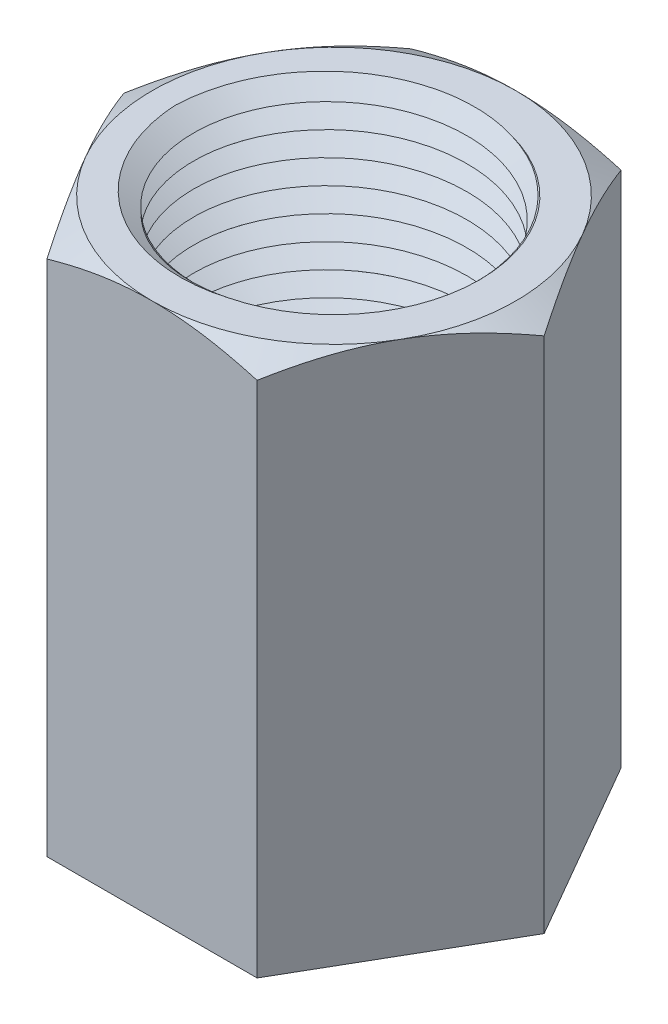
SolidWorks part; units mm, degrees
ref_plane "Front Plane" through (0, 0, 0) normal (0, 0, 1) x (1, 0, 0)
ref_plane "Top Plane" through (0, 0, 0) normal (0, 1, 0) x (1, 0, 0)
ref_plane "Right Plane" through (0, 0, 0) normal (1, 0, 0) x (0, 0, -1)
sketch "Sketch1" plane through (0, 0, 0) normal (0, 1, 0) x (1, 0, 0)
  line L1 (8.6603, 0) -> (4.3301, 7.5)
  line L2 (4.3301, 7.5) -> (-4.3301, 7.5)
  line L3 (-4.3301, 7.5) -> (-8.6603, 0)
  line L4 (-8.6603, 0) -> (-4.3301, -7.5)
  line L5 (-4.3301, -7.5) -> (4.3301, -7.5)
  line L6 (4.3301, -7.5) -> (8.6603, 0)
  circle A0 centre (0, 0) radius 7.5 construction
  dimension "D1" = 15
extrude "Boss-Extrude1" add sketch "Sketch1" along normal blind 22
sketch "Sketch2" plane through (0, 22, 0) normal (0, 1, 0) x (1, 0, 0)
  circle A0 centre (0, 0) radius 5.5
  dimension "D1" = 11
extrude "Cut-Extrude1" cut sketch "Sketch2" against normal blind 22
sketch "Sketch3" plane through (0, 22, 0) normal (0, 1, 0) x (1, 0, 0)
  circle A0 centre (0, 0) radius 7.5
extrude "Cut-Extrude2" cut sketch "Sketch3" against normal blind 1 draft 60 flip side to cut contours A0
chamfer "Chamfer2" distance 0.5 angle 45 1 edges at (0, 22, 5.5)
ref_plane "Plane1" through (0, 32, 0) normal (0, 1, 0) x (1, 0, 0)
sketch "Sketch4" plane through (0, 32, 0) normal (0, 1, 0) x (1, 0, 0)
  circle A0 centre (0, 0) radius 5.5 construction
  circle A1 centre (0, 0) radius 5.5
curve "Helix/Spiral1" pitch 1 height 34 radius 5.5 centre (0, 32, 0) axis (0, -1, 0) start towards (0, 0, 1)
sketch "Sketch6" plane through (0, 0, 0) normal (0, 0, 1) x (1, 0, 0)
  line L1 (-6.5, 32) -> (-5, 31.134)
  line L2 (-5, 31.134) -> (-5, 32.866)
  line L3 (-5, 32.866) -> (-6.5, 32)
  circle A0 centre (-5.5, 32) radius 0.5 construction
  spline S0 degree 3 poles (-5.5, 32) (-5.5, 31.9793) (-5.2126, 31.9373) (-3.9849, 31.8748) (-2.1484, 31.8122) (0.0163, 31.7495) (2.1786, 31.6869) (4.008, 31.6243) (5.225, 31.5617) (5.6436, 31.4991) (5.2, 31.4365) (3.9617, 31.3738) (2.1182, 31.3112) (-0.049, 31.2486) (-2.2087, 31.186) (-4.0309, 31.1234) (-5.2372, 31.0608) (-5.6433, 30.9982) (-5.1872, 30.9355) (-3.9384, 30.8729) (-2.0879, 30.8103) (0.0816, 30.7477) (2.2387, 30.6851) (4.0537, 30.6225) (5.2493, 30.5599) (5.6429, 30.4972) (5.1742, 30.4346) (3.915, 30.372) (2.0575, 30.3094) (-0.1143, 30.2468) (-2.2686, 30.1842) (-4.0764, 30.1215) (-5.2612, 30.0589) (-5.6422, 29.9963) (-5.1611, 29.9337) (-3.8914, 29.8711) (-2.0271, 29.8085) (0.1469, 29.7459) (2.2985, 29.6832) (4.0989, 29.6206) (5.273, 29.558) (5.6414, 29.4954) (5.1478, 29.4328) (3.8677, 29.3702) (1.9966, 29.3076) (-0.1796, 29.2449) (-2.3283, 29.1823) (-4.1212, 29.1197) (-5.2845, 29.0571) (-5.6403, 28.9945) (-5.1343, 28.9319) (-3.8438, 28.8692) (-1.966, 28.8066) (0.2122, 28.744) (2.358, 28.6814) (4.1435, 28.6188) (5.2959, 28.5562) (5.6391, 28.4936) (5.1207, 28.4309) (3.8199, 28.3683) (1.9354, 28.3057) (-0.2448, 28.2431) (-2.3876, 28.1805) (-4.1656, 28.1179) (-5.3071, 28.0552) (-5.6377, 27.9926) (-5.1069, 27.93) (-3.7958, 27.8674) (-1.9047, 27.8048) (0.2774, 27.7422) (2.4172, 27.6796) (4.1875, 27.6169) (5.3181, 27.5543) (5.6361, 27.4917) (5.0929, 27.4291) (3.7715, 27.3665) (1.8739, 27.3039) (-0.31, 27.2413) (-2.4466, 27.1786) (-4.2094, 27.116) (-5.3289, 27.0534) (-5.6343, 26.9908) (-5.0787, 26.9282) (-3.7472, 26.8656) (-1.8431, 26.8029) (0.3426, 26.7403) (2.476, 26.6777) (4.231, 26.6151) (5.3396, 26.5525) (5.6323, 26.4899) (5.0644, 26.4273) (3.7227, 26.3646) (1.8122, 26.302) (-0.3752, 26.2394) (-2.5053, 26.1768) (-4.2526, 26.1142) (-5.3501, 26.0516) (-5.6301, 25.989) (-5.0499, 25.9263) (-3.6981, 25.8637) (-1.7812, 25.8011) (0.4078, 25.7385) (2.5345, 25.6759) (4.274, 25.6133) (5.3604, 25.5506) (5.6278, 25.488) (5.0352, 25.4254) (3.6734, 25.3628) (1.7502, 25.3002) (-0.4404, 25.2376) (-2.5637, 25.175) (-4.2952, 25.1123) (-5.3705, 25.0497) (-5.6252, 24.9871) (-5.0204, 24.9245) (-3.6485, 24.8619) (-1.7191, 24.7993) (0.4729, 24.7366) (2.5927, 24.674) (4.3163, 24.6114) (5.3805, 24.5488) (5.6225, 24.4862) (5.0054, 24.4236) (3.6235, 24.361) (1.688, 24.2983) (-0.5054, 24.2357) (-2.6217, 24.1731) (-4.3373, 24.1105) (-5.3902, 24.0479) (-5.6196, 23.9853) (-4.9902, 23.9227) (-3.5985, 23.86) (-1.6568, 23.7974) (0.5379, 23.7348) (2.6505, 23.6722) (4.3581, 23.6096) (5.3998, 23.547) (5.6164, 23.4843) (4.9749, 23.4217) (3.5732, 23.3591) (1.6256, 23.2965) (-0.5704, 23.2339) (-2.6793, 23.1713) (-4.3788, 23.1087) (-5.4092, 23.046) (-5.6131, 22.9834) (-4.9594, 22.9208) (-3.5479, 22.8582) (-1.5943, 22.7956) (0.6029, 22.733) (2.708, 22.6703) (4.3993, 22.6077) (5.4184, 22.5451) (5.6097, 22.4825) (4.9437, 22.4199) (3.5224, 22.3573) (1.5629, 22.2947) (-0.6354, 22.232) (-2.7366, 22.1694) (-4.4197, 22.1068) (-5.4275, 22.0442) (-5.606, 21.9816) (-4.9279, 21.919) (-3.4969, 21.8564) (-1.5315, 21.7937) (0.6678, 21.7311) (2.7651, 21.6685) (4.4399, 21.6059) (5.4363, 21.5433) (5.6021, 21.4807) (4.9119, 21.418) (3.4712, 21.3554) (1.5001, 21.2928) (-0.7002, 21.2302) (-2.7935, 21.1676) (-4.46, 21.105) (-5.445, 21.0424) (-5.5981, 20.9797) (-4.8957, 20.9171) (-3.4454, 20.8545) (-1.4686, 20.7919) (0.7326, 20.7293) (2.8219, 20.6667) (4.4799, 20.6041) (5.4535, 20.5414) (5.5938, 20.4788) (4.8794, 20.4162) (3.4195, 20.3536) (1.437, 20.291) (-0.765, 20.2284) (-2.8501, 20.1657) (-4.4997, 20.1031) (-5.4618, 20.0405) (-5.5894, 19.9779) (-4.8629, 19.9153) (-3.3934, 19.8527) (-1.4054, 19.7901) (0.7973, 19.7274) (2.8782, 19.6648) (4.5194, 19.6022) (5.47, 19.5396) (5.5848, 19.477) (4.8463, 19.4144) (3.3673, 19.3517) (1.3738, 19.2891) (-0.8296, 19.2265) (-2.9063, 19.1639) (-4.5388, 19.1013) (-5.4779, 19.0387) (-5.58, 18.9761) (-4.8295, 18.9134) (-3.341, 18.8508) (-1.3421, 18.7882) (0.8619, 18.7256) (2.9342, 18.663) (4.5582, 18.6004) (5.4857, 18.5378) (5.575, 18.4751) (4.8125, 18.4125) (3.3147, 18.3499) (1.3104, 18.2873) (-0.8942, 18.2247) (-2.962, 18.1621) (-4.5774, 18.0994) (-5.4933, 18.0368) (-5.5698, 17.9742) (-4.7954, 17.9116) (-3.2882, 17.849) (-1.2786, 17.7864) (0.9264, 17.7238) (2.9898, 17.6611) (4.5964, 17.5985) (5.5007, 17.5359) (5.5645, 17.4733) (4.7781, 17.4107) (3.2616, 17.3481) (1.2467, 17.2855) (-0.9586, 17.2228) (-3.0174, 17.1602) (-4.6152, 17.0976) (-5.5079, 17.035) (-5.5589, 16.9724) (-4.7606, 16.9098) (-3.2349, 16.8471) (-1.2149, 16.7845) (0.9907, 16.7219) (3.045, 16.6593) (4.634, 16.5967) (5.5149, 16.5341) (5.5532, 16.4715) (4.743, 16.4088) (3.2081, 16.3462) (1.183, 16.2836) (-1.0229, 16.221) (-3.0724, 16.1584) (-4.6525, 16.0958) (-5.5217, 16.0331) (-5.5473, 15.9705) (-4.7252, 15.9079) (-3.1811, 15.8453) (-1.151, 15.7827) (1.055, 15.7201) (3.0998, 15.6575) (4.6709, 15.5948) (5.5284, 15.5322) (5.5412, 15.4696) (4.7073, 15.407) (3.1541, 15.3444) (1.119, 15.2818) (-1.087, 15.2192) (-3.127, 15.1565) (-4.6892, 15.0939) (-5.5349, 15.0313) (-5.5349, 14.9687) (-4.6892, 14.9061) (-3.127, 14.8435) (-1.087, 14.7808) (1.119, 14.7182) (3.1541, 14.6556) (4.7073, 14.593) (5.5412, 14.5304) (5.5284, 14.4678) (4.6709, 14.4052) (3.0998, 14.3425) (1.055, 14.2799) (-1.151, 14.2173) (-3.1811, 14.1547) (-4.7252, 14.0921) (-5.5473, 14.0295) (-5.5217, 13.9669) (-4.6525, 13.9042) (-3.0724, 13.8416) (-1.0229, 13.779) (1.183, 13.7164) (3.2081, 13.6538) (4.743, 13.5912) (5.5532, 13.5285) (5.5149, 13.4659) (4.634, 13.4033) (3.045, 13.3407) (0.9907, 13.2781) (-1.2149, 13.2155) (-3.2349, 13.1529) (-4.7606, 13.0902) (-5.5589, 13.0276) (-5.5079, 12.965) (-4.6152, 12.9024) (-3.0174, 12.8398) (-0.9586, 12.7772) (1.2467, 12.7145) (3.2616, 12.6519) (4.7781, 12.5893) (5.5645, 12.5267) (5.5007, 12.4641) (4.5964, 12.4015) (2.9898, 12.3389) (0.9264, 12.2762) (-1.2786, 12.2136) (-3.2882, 12.151) (-4.7954, 12.0884) (-5.5698, 12.0258) (-5.4933, 11.9632) (-4.5774, 11.9006) (-2.962, 11.8379) (-0.8942, 11.7753) (1.3104, 11.7127) (3.3147, 11.6501) (4.8125, 11.5875) (5.575, 11.5249) (5.4857, 11.4622) (4.5582, 11.3996) (2.9342, 11.337) (0.8619, 11.2744) (-1.3421, 11.2118) (-3.341, 11.1492) (-4.8295, 11.0866) (-5.58, 11.0239) (-5.4779, 10.9613) (-4.5388, 10.8987) (-2.9063, 10.8361) (-0.8296, 10.7735) (1.3738, 10.7109) (3.3673, 10.6483) (4.8463, 10.5856) (5.5848, 10.523) (5.47, 10.4604) (4.5194, 10.3978) (2.8782, 10.3352) (0.7973, 10.2726) (-1.4054, 10.2099) (-3.3934, 10.1473) (-4.8629, 10.0847) (-5.5894, 10.0221) (-5.4618, 9.9595) (-4.4997, 9.8969) (-2.8501, 9.8343) (-0.765, 9.7716) (1.437, 9.709) (3.4195, 9.6464) (4.8794, 9.5838) (5.5938, 9.5212) (5.4535, 9.4586) (4.4799, 9.3959) (2.8219, 9.3333) (0.7326, 9.2707) (-1.4686, 9.2081) (-3.4454, 9.1455) (-4.8957, 9.0829) (-5.5981, 9.0203) (-5.445, 8.9576) (-4.46, 8.895) (-2.7935, 8.8324) (-0.7002, 8.7698) (1.5001, 8.7072) (3.4712, 8.6446) (4.9119, 8.582) (5.6021, 8.5193) (5.4363, 8.4567) (4.4399, 8.3941) (2.7651, 8.3315) (0.6678, 8.2689) (-1.5315, 8.2063) (-3.4969, 8.1436) (-4.9279, 8.081) (-5.606, 8.0184) (-5.4275, 7.9558) (-4.4197, 7.8932) (-2.7366, 7.8306) (-0.6354, 7.768) (1.5629, 7.7053) (3.5224, 7.6427) (4.9437, 7.5801) (5.6097, 7.5175) (5.4184, 7.4549) (4.3993, 7.3923) (2.708, 7.3297) (0.6029, 7.267) (-1.5943, 7.2044) (-3.5479, 7.1418) (-4.9594, 7.0792) (-5.6131, 7.0166) (-5.4092, 6.954) (-4.3788, 6.8913) (-2.6793, 6.8287) (-0.5704, 6.7661) (1.6256, 6.7035) (3.5732, 6.6409) (4.9749, 6.5783) (5.6164, 6.5157) (5.3998, 6.453) (4.3581, 6.3904) (2.6505, 6.3278) (0.5379, 6.2652) (-1.6568, 6.2026) (-3.5985, 6.14) (-4.9902, 6.0773) (-5.6196, 6.0147) (-5.3902, 5.9521) (-4.3373, 5.8895) (-2.6217, 5.8269) (-0.5054, 5.7643) (1.688, 5.7017) (3.6235, 5.639) (5.0054, 5.5764) (5.6225, 5.5138) (5.3805, 5.4512) (4.3163, 5.3886) (2.5927, 5.326) (0.4729, 5.2634) (-1.7191, 5.2007) (-3.6485, 5.1381) (-5.0204, 5.0755) (-5.6252, 5.0129) (-5.3705, 4.9503) (-4.2952, 4.8877) (-2.5637, 4.825) (-0.4404, 4.7624) (1.7502, 4.6998) (3.6734, 4.6372) (5.0352, 4.5746) (5.6278, 4.512) (5.3604, 4.4494) (4.274, 4.3867) (2.5345, 4.3241) (0.4078, 4.2615) (-1.7812, 4.1989) (-3.6981, 4.1363) (-5.0499, 4.0737) (-5.6301, 4.011) (-5.3501, 3.9484) (-4.2526, 3.8858) (-2.5053, 3.8232) (-0.3752, 3.7606) (1.8122, 3.698) (3.7227, 3.6354) (5.0644, 3.5727) (5.6323, 3.5101) (5.3396, 3.4475) (4.231, 3.3849) (2.476, 3.3223) (0.3426, 3.2597) (-1.8431, 3.1971) (-3.7472, 3.1344) (-5.0787, 3.0718) (-5.6343, 3.0092) (-5.3289, 2.9466) (-4.2094, 2.884) (-2.4466, 2.8214) (-0.31, 2.7587) (1.8739, 2.6961) (3.7715, 2.6335) (5.0929, 2.5709) (5.6361, 2.5083) (5.3181, 2.4457) (4.1875, 2.3831) (2.4172, 2.3204) (0.2774, 2.2578) (-1.9047, 2.1952) (-3.7958, 2.1326) (-5.1069, 2.07) (-5.6377, 2.0074) (-5.3071, 1.9448) (-4.1656, 1.8821) (-2.3876, 1.8195) (-0.2448, 1.7569) (1.9354, 1.6943) (3.8199, 1.6317) (5.1207, 1.5691) (5.6391, 1.5064) (5.2959, 1.4438) (4.1435, 1.3812) (2.358, 1.3186) (0.2122, 1.256) (-1.966, 1.1934) (-3.8438, 1.1308) (-5.1343, 1.0681) (-5.6403, 1.0055) (-5.2845, 0.9429) (-4.1212, 0.8803) (-2.3283, 0.8177) (-0.1796, 0.7551) (1.9966, 0.6924) (3.8677, 0.6298) (5.1478, 0.5672) (5.6414, 0.5046) (5.273, 0.442) (4.0989, 0.3794) (2.2985, 0.3168) (0.1469, 0.2541) (-2.0271, 0.1915) (-3.8914, 0.1289) (-5.1611, 0.0663) (-5.6422, 0.0037) (-5.2612, -0.0589) (-4.0764, -0.1215) (-2.2686, -0.1842) (-0.1143, -0.2468) (2.0575, -0.3094) (3.915, -0.372) (5.1742, -0.4346) (5.6429, -0.4972) (5.2493, -0.5599) (4.0537, -0.6225) (2.2387, -0.6851) (0.0816, -0.7477) (-2.0879, -0.8103) (-3.9384, -0.8729) (-5.1872, -0.9355) (-5.6433, -0.9982) (-5.2372, -1.0608) (-4.0309, -1.1234) (-2.2087, -1.186) (-0.049, -1.2486) (2.1182, -1.3112) (3.9617, -1.3738) (5.2, -1.4365) (5.6436, -1.4991) (5.225, -1.5617) (4.008, -1.6243) (2.1786, -1.6869) (0.0163, -1.7495) (-2.1484, -1.8122) (-3.9849, -1.8748) (-5.2126, -1.9373) (-5.5, -1.9793) (-5.5, -2) knots 0 0 0 0 0.001842 0.003683 0.005525 0.007366 0.009208 0.01105 0.012891 0.014733 0.016575 0.018416 0.020258 0.022099 0.023941 0.025783 0.027624 0.029466 0.031308 0.033149 0.034991 0.036832 0.038674 0.040516 0.042357 0.044199 0.046041 0.047882 0.049724 0.051565 0.053407 0.055249 0.05709 0.058932 0.060773 0.062615 0.064457 0.066298 0.06814 0.069982 0.071823 0.073665 0.075506 0.077348 0.07919 0.081031 0.082873 0.084715 0.086556 0.088398 0.090239 0.092081 0.093923 0.095764 0.097606 0.099448 0.101289 0.103131 0.104972 0.106814 0.108656 0.110497 0.112339 0.11418 0.116022 0.117864 0.119705 0.121547 0.123389 0.12523 0.127072 0.128913 0.130755 0.132597 0.134438 0.13628 0.138122 0.139963 0.141805 0.143646 0.145488 0.14733 0.149171 0.151013 0.152855 0.154696 0.156538 0.158379 0.160221 0.162063 0.163904 0.165746 0.167587 0.169429 0.171271 0.173112 0.174954 0.176796 0.178637 0.180479 0.18232 0.184162 0.186004 0.187845 0.189687 0.191529 0.19337 0.195212 0.197053 0.198895 0.200737 0.202578 0.20442 0.206262 0.208103 0.209945 0.211786 0.213628 0.21547 0.217311 0.219153 0.220994 0.222836 0.224678 0.226519 0.228361 0.230203 0.232044 0.233886 0.235727 0.237569 0.239411 0.241252 0.243094 0.244936 0.246777 0.248619 0.25046 0.252302 0.254144 0.255985 0.257827 0.259669 0.26151 0.263352 0.265193 0.267035 0.268877 0.270718 0.27256 0.274401 0.276243 0.278085 0.279926 0.281768 0.28361 0.285451 0.287293 0.289134 0.290976 0.292818 0.294659 0.296501 0.298343 0.300184 0.302026 0.303867 0.305709 0.307551 0.309392 0.311234 0.313076 0.314917 0.316759 0.3186 0.320442 0.322284 0.324125 0.325967 0.327808 0.32965 0.331492 0.333333 0.335175 0.337017 0.338858 0.3407 0.342541 0.344383 0.346225 0.348066 0.349908 0.35175 0.353591 0.355433 0.357274 0.359116 0.360958 0.362799 0.364641 0.366483 0.368324 0.370166 0.372007 0.373849 0.375691 0.377532 0.379374 0.381215 0.383057 0.384899 0.38674 0.388582 0.390424 0.392265 0.394107 0.395948 0.39779 0.399632 0.401473 0.403315 0.405157 0.406998 0.40884 0.410681 0.412523 0.414365 0.416206 0.418048 0.41989 0.421731 0.423573 0.425414 0.427256 0.429098 0.430939 0.432781 0.434622 0.436464 0.438306 0.440147 0.441989 0.443831 0.445672 0.447514 0.449355 0.451197 0.453039 0.45488 0.456722 0.458564 0.460405 0.462247 0.464088 0.46593 0.467772 0.469613 0.471455 0.473297 0.475138 0.47698 0.478821 0.480663 0.482505 0.484346 0.486188 0.488029 0.489871 0.491713 0.493554 0.495396 0.497238 0.499079 0.500921 0.502762 0.504604 0.506446 0.508287 0.510129 0.511971 0.513812 0.515654 0.517495 0.519337 0.521179 0.52302 0.524862 0.526703 0.528545 0.530387 0.532228 0.53407 0.535912 0.537753 0.539595 0.541436 0.543278 0.54512 0.546961 0.548803 0.550645 0.552486 0.554328 0.556169 0.558011 0.559853 0.561694 0.563536 0.565378 0.567219 0.569061 0.570902 0.572744 0.574586 0.576427 0.578269 0.58011 0.581952 0.583794 0.585635 0.587477 0.589319 0.59116 0.593002 0.594843 0.596685 0.598527 0.600368 0.60221 0.604052 0.605893 0.607735 0.609576 0.611418 0.61326 0.615101 0.616943 0.618785 0.620626 0.622468 0.624309 0.626151 0.627993 0.629834 0.631676 0.633517 0.635359 0.637201 0.639042 0.640884 0.642726 0.644567 0.646409 0.64825 0.650092 0.651934 0.653775 0.655617 0.657459 0.6593 0.661142 0.662983 0.664825 0.666667 0.668508 0.67035 0.672192 0.674033 0.675875 0.677716 0.679558 0.6814 0.683241 0.685083 0.686924 0.688766 0.690608 0.692449 0.694291 0.696133 0.697974 0.699816 0.701657 0.703499 0.705341 0.707182 0.709024 0.710866 0.712707 0.714549 0.71639 0.718232 0.720074 0.721915 0.723757 0.725599 0.72744 0.729282 0.731123 0.732965 0.734807 0.736648 0.73849 0.740331 0.742173 0.744015 0.745856 0.747698 0.74954 0.751381 0.753223 0.755064 0.756906 0.758748 0.760589 0.762431 0.764273 0.766114 0.767956 0.769797 0.771639 0.773481 0.775322 0.777164 0.779006 0.780847 0.782689 0.78453 0.786372 0.788214 0.790055 0.791897 0.793738 0.79558 0.797422 0.799263 0.801105 0.802947 0.804788 0.80663 0.808471 0.810313 0.812155 0.813996 0.815838 0.81768 0.819521 0.821363 0.823204 0.825046 0.826888 0.828729 0.830571 0.832413 0.834254 0.836096 0.837937 0.839779 0.841621 0.843462 0.845304 0.847145 0.848987 0.850829 0.85267 0.854512 0.856354 0.858195 0.860037 0.861878 0.86372 0.865562 0.867403 0.869245 0.871087 0.872928 0.87477 0.876611 0.878453 0.880295 0.882136 0.883978 0.88582 0.887661 0.889503 0.891344 0.893186 0.895028 0.896869 0.898711 0.900552 0.902394 0.904236 0.906077 0.907919 0.909761 0.911602 0.913444 0.915285 0.917127 0.918969 0.92081 0.922652 0.924494 0.926335 0.928177 0.930018 0.93186 0.933702 0.935543 0.937385 0.939227 0.941068 0.94291 0.944751 0.946593 0.948435 0.950276 0.952118 0.953959 0.955801 0.957643 0.959484 0.961326 0.963168 0.965009 0.966851 0.968692 0.970534 0.972376 0.974217 0.976059 0.977901 0.979742 0.981584 0.983425 0.985267 0.987109 0.98895 0.990792 0.992634 0.994475 0.996317 0.998158 1 1 1 1 construction
  dimension "D1" = 1
sweep "Cut-Sweep3" cut profiles "Sketch6" path "Helix/Spiral1" align with end faces yes
